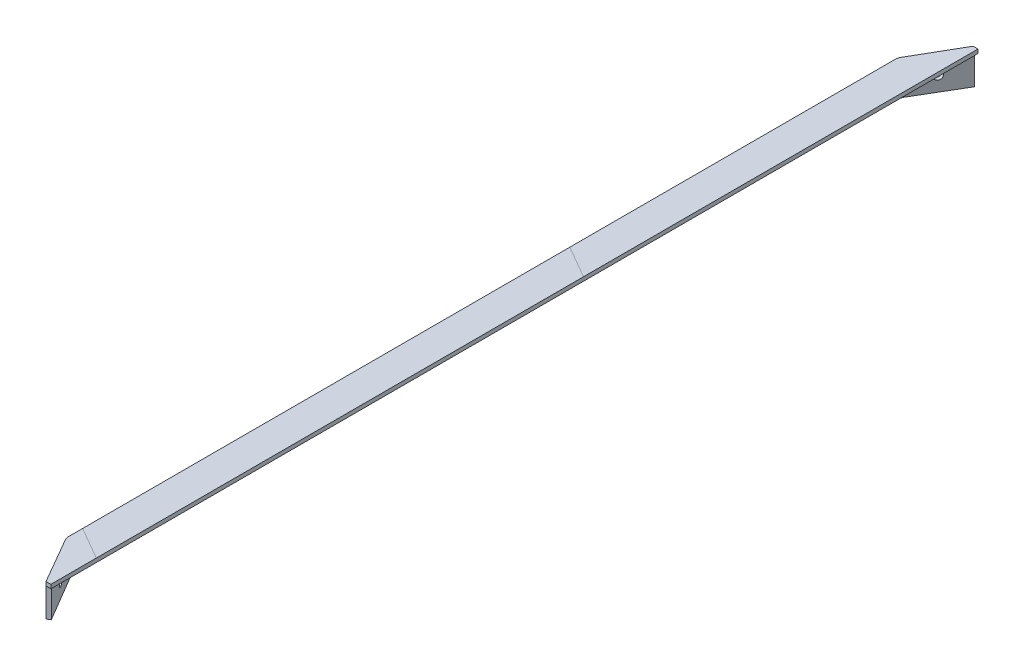
SolidWorks part; units mm, degrees
material "1.0116 (S235J2G3)"
ref_plane "Front Plane" through (0, 0, 0) normal (0, 0, 1) x (1, 0, 0)
ref_plane "Top Plane" through (0, 0, 0) normal (0, 1, 0) x (1, 0, 0)
ref_plane "Right Plane" through (0, 0, 0) normal (1, 0, 0) x (0, 0, -1)
sketch "Sketch1" plane through (0, 0, 0) normal (0, 0, 1) x (1, 0, 0)
  line L1 (44, 6) -> (44, 0)
  line L2 (44, 0) -> (0, 0)
  line L3 (0, 0) -> (0, -44)
  line L4 (0, -44) -> (-6, -44)
  line L6 (-6, -44) -> (-6, 6)
  line L7 (-6, 6) -> (44, 6)
  dimension "D1" = 0
  dimension "D2" = 6
  dimension "D3" = 6
  dimension "D4" = 6
  dimension "D5" = 50
  dimension "D6" = 50
  dimension "D7" = 0
extrude "Boss-Extrude1" add sketch "Sketch1" along normal blind 640
sketch "Sketch4" plane through (0, 0, 0) normal (0, 1, 0) x (1, 0, 0)
  line L0 (-6, -640) -> (36.5, -713.6122)
  line L1 (36.5, -713.6122) -> (44, -713.6122)
  line L2 (44, -713.6122) -> (44, -640)
  line L3 (44, -640) -> (-6, -640)
  line L4 (-6, -640) -> (-6, 0) construction
  dimension "D1" = 210
  dimension "D2" = 90
  dimension "D3" = 85
extrude "Boss-Extrude2" add sketch "Sketch4" along normal blind 6
sketch "Sketch5" plane through (0, 0, 0) normal (0, -1, 0) x (1, 0, 0)
  line L0 (-6, 640) -> (36.5, 713.6122)
  line L1 (36.5, 713.6122) -> (41.6962, 710.6122)
  line L3 (41.6962, 710.6122) -> (0, 640)
  line L4 (0, 640) -> (0, 0) construction
  line L5 (0, 640) -> (0, 0) construction
  line L6 (0, 640) -> (-6, 640)
  dimension "D1" = 6
extrude "Boss-Extrude3" add sketch "Sketch5" along normal blind 44
sketch "Sketch6" plane through (-280.2115, 0, 165.4636) normal (0.8611, 0, -0.5085) x (-0.5085, 0, -0.8611)
  line L0 (-551.0928, -44) -> (-633.0968, -44) construction
  line L1 (-633.0968, -44) -> (-633.0968, 0) construction
  circle A0 centre (-592.0968, -22) radius 6
  dimension "D1" = 12
  dimension "D2" = 22
  dimension "D3" = 41
extrude "Cut-Extrude1" cut sketch "Sketch6" against normal blind 6
mirror "Mirror4" about plane through (0, 0, 0) normal (0, 0, 1) of "Boss-Extrude2", "Cut-Extrude1", "Boss-Extrude3", "Boss-Extrude1"
fillet "Fillet1" radius 10 4 edges at (-6, -19, 640) (-6, -19, -640) (0, -22, -640) (0, -22, 640)
sketch "Sketch8" plane through (0, 6, 0) normal (0, 1, 0) x (1, 0, 0)
  line L0 (-6, -614.7446) -> (44, -643.6122)
  line L1 (-6, -637.3205) -> (-6, 637.3205) construction
  line L2 (44, -713.6122) -> (44, 713.6122) construction
  line L3 (44, -643.6122) -> (44, 106.3878)
  line L4 (44, 106.3878) -> (-6, 135.2554)
  line L5 (-6, 135.2554) -> (-6, -614.7446)
  line L6 (36.5, -713.6122) -> (44, -713.6122) construction
  dimension "D1" = 60
  dimension "D2" = 60
  dimension "D3" = 750
  dimension "D4" = 70
split line "Split Line1"
